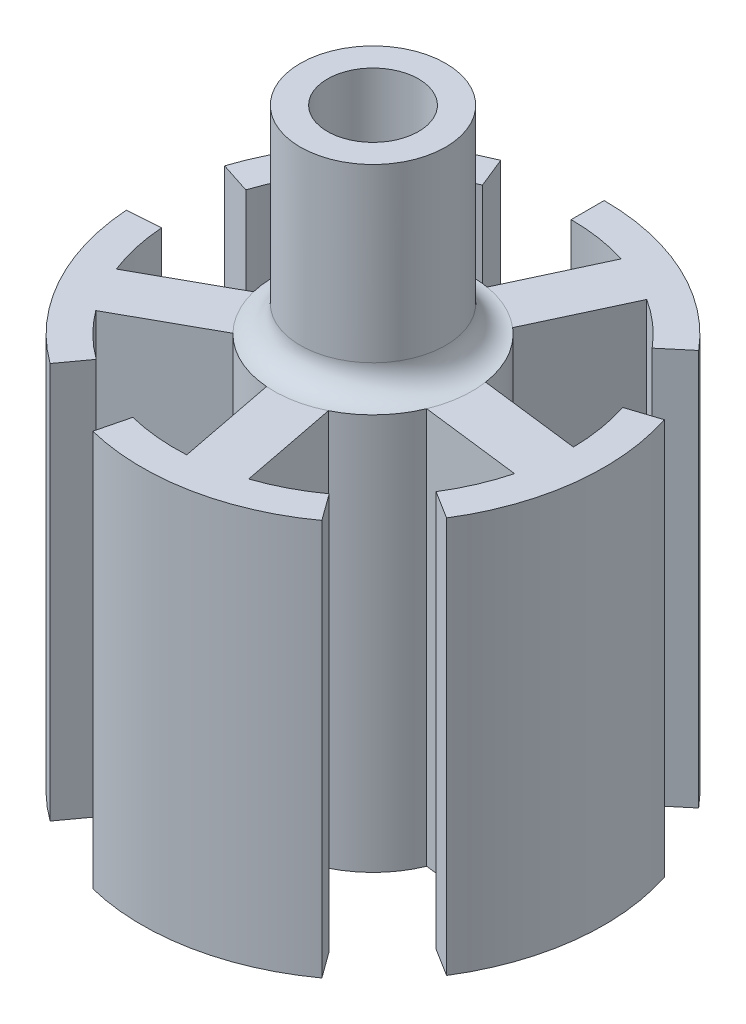
SolidWorks part; units mm, degrees
ref_plane "Front Plane" through (0, 0, 0) normal (0, 0, 1) x (1, 0, 0)
ref_plane "Top Plane" through (0, 0, 0) normal (0, 1, 0) x (1, 0, 0)
ref_plane "Right Plane" through (0, 0, 0) normal (1, 0, 0) x (0, 0, -1)
sketch "Sketch1" plane through (0, 0, 0) normal (0, 1, 0) x (1, 0, 0)
  line L0 (0, 17.5) -> (0, 15)
  line L1 (11.4907, 9.6418) -> (13.4058, 11.2488)
  line L2 (16.6435, 5.4078) -> (14.2658, 4.6353)
  line L3 (12.7207, -7.9488) -> (14.8408, -9.2736)
  line L4 (10.2862, -14.1578) -> (8.8168, -12.1353)
  line L5 (-3.6288, -14.5544) -> (-4.2336, -16.9802)
  line L6 (-10.2862, -14.1578) -> (-8.8168, -12.1353)
  line L7 (-14.9635, -1.0463) -> (-17.4574, -1.2207)
  line L8 (-16.6435, 5.4078) -> (-14.2658, 4.6353)
  line L9 (-5.6191, 13.9078) -> (-6.5556, 16.2257)
  arc A0 (0, 17.5) -> (13.4058, 11.2488) centre (0, 0) cw
  arc A1 (11.4907, 9.6418) -> (0, 15) centre (0, 0) ccw
  arc A2 (16.6435, 5.4078) -> (14.8408, -9.2736) centre (0, 0) cw
  arc A3 (12.7207, -7.9488) -> (14.2658, 4.6353) centre (0, 0) ccw
  arc A4 (10.2862, -14.1578) -> (-4.2336, -16.9802) centre (0, 0) cw
  arc A5 (-3.6288, -14.5544) -> (8.8168, -12.1353) centre (0, 0) ccw
  arc A6 (-10.2862, -14.1578) -> (-17.4574, -1.2207) centre (0, 0) cw
  arc A7 (-14.9635, -1.0463) -> (-8.8168, -12.1353) centre (0, 0) ccw
  arc A8 (-16.6435, 5.4078) -> (-6.5556, 16.2257) centre (0, 0) cw
  arc A9 (-5.6191, 13.9078) -> (-14.2658, 4.6353) centre (0, 0) ccw
  point P25 (0, 0)
  dimension "D1" = 5
extrude "Boss-Extrude2" add sketch "Sketch1" along normal blind 30
sketch "Sketch2" plane through (0, 0, 0) normal (0, 1, 0) x (1, 0, 0)
  line L0 (8.1519, 12.7494) -> (4.5267, 14.4399)
  line L1 (8.1519, 12.7494) -> (1.8723, -0.7172)
  line L2 (4.5267, 14.4399) -> (-1.7529, 0.9732)
  line L3 (1.8723, -0.7172) -> (-1.7529, 0.9732)
  line L4 (14.6445, -3.8131) -> (15.1319, 0.1571)
  line L5 (14.6445, -3.8131) -> (-0.1036, -2.0023)
  line L6 (15.1319, 0.1571) -> (0.3839, 1.9679)
  line L7 (-0.1036, -2.0023) -> (0.3839, 1.9679)
  line L8 (0.8989, -15.106) -> (4.8254, -14.3428)
  line L9 (0.8989, -15.106) -> (-1.9363, -0.5203)
  line L10 (4.8254, -14.3428) -> (1.9902, 0.243)
  line L11 (-1.9363, -0.5203) -> (1.9902, 0.243)
  line L12 (-14.0889, -5.5229) -> (-12.1497, -9.0214)
  line L13 (-14.0889, -5.5229) -> (-1.0931, 1.6808)
  line L14 (-12.1497, -9.0214) -> (0.8461, -1.8177)
  line L15 (-1.0931, 1.6808) -> (0.8461, -1.8177)
  line L16 (-9.6063, 11.6927) -> (-12.3343, 8.7673)
  line L17 (-9.6063, 11.6927) -> (1.2607, 1.559)
  line L18 (-12.3343, 8.7673) -> (-1.4673, -1.3664)
  line L19 (1.2607, 1.559) -> (-1.4673, -1.3664)
  arc A0 (11.4907, 9.6418) -> (0, 15) centre (0, 0) ccw construction
  point P8 (6.3393, 13.5946)
  point P27 (0, 0)
  dimension "D1" = 5
extrude "Boss-Extrude3" add sketch "Sketch2" along normal blind 30 contours L2 L17 L6 L1 L0 | L16 L18 L13 L2 L17 | L18 L13 L12 L14 L9 | L14 L9 L8 L10 L5 | L10 L5 L4 L6 L1 | L7 L15 L14 L5 L10 L1 L3 L11 | L19 L17 L6 L7 | L17 L19 L7 L3 L11 L10 L1 L6 | L19 L7 L6 L17 L2 L13 L15 L3 | L15 L13 L2 L3 | L11 L3 L1 L10 | L11 L19 L18 L9 L14 L5 L7 L15 | L19 L15 L3 L2 L13 L18 L9 L11 | L19 L11 L9 L18 | L15 L7 L5 L14 | L7 L6 L4 L5 | L2 L3 L1 L0 | L15 L14 L12 L13 region at (3.6821, 0, -7.8962) region at (8.6476, 0, 1.0618) region at (1.5876, 0, -0.88) region at (-0.3464, 0, -1.7818) region at (-6.3719, 0, -5.9419) region at (1.3275, 0, 1.2379) region at (1.4907, 0, 0.183) region at (0.6347, 0, -1.3612) region at (-1.0984, 0, -1.0243) region at (-1.8016, 0, -0.2212) region at (1.6624, 0, 8.5524) region at (-7.6201, 0, 4.2239) region at (-0.7671, 0, 1.6451) region at (0.2866, 0, 1.4743) region at (-1.3136, 0, 0.7281)
sketch "Sketch3" plane through (0, 0, 0) normal (0, 1, 0) x (1, 0, 0)
  circle A0 centre (0, 0) radius 7.5
extrude "Boss-Extrude4" add sketch "Sketch3" along normal blind 30
ref_plane "Plane2" through (0, 30, 0) normal (0, 1, 0) x (1, 0, 0)
sketch "Sketch5" plane through (0, 30, 0) normal (0, 1, 0) x (1, 0, 0)
  circle A0 centre (0, 0) radius 5.5
extrude "Boss-Extrude5" add sketch "Sketch5" along normal blind 15
sketch "Sketch4" plane through (0, 0, 0) normal (0, 1, 0) x (1, 0, 0)
  circle A0 centre (0, 0) radius 3.45
extrude "Cut-Extrude1" cut sketch "Sketch4" along normal through all
fillet "Fillet1" radius 2 1 edges at (0, 30, -5.5)
